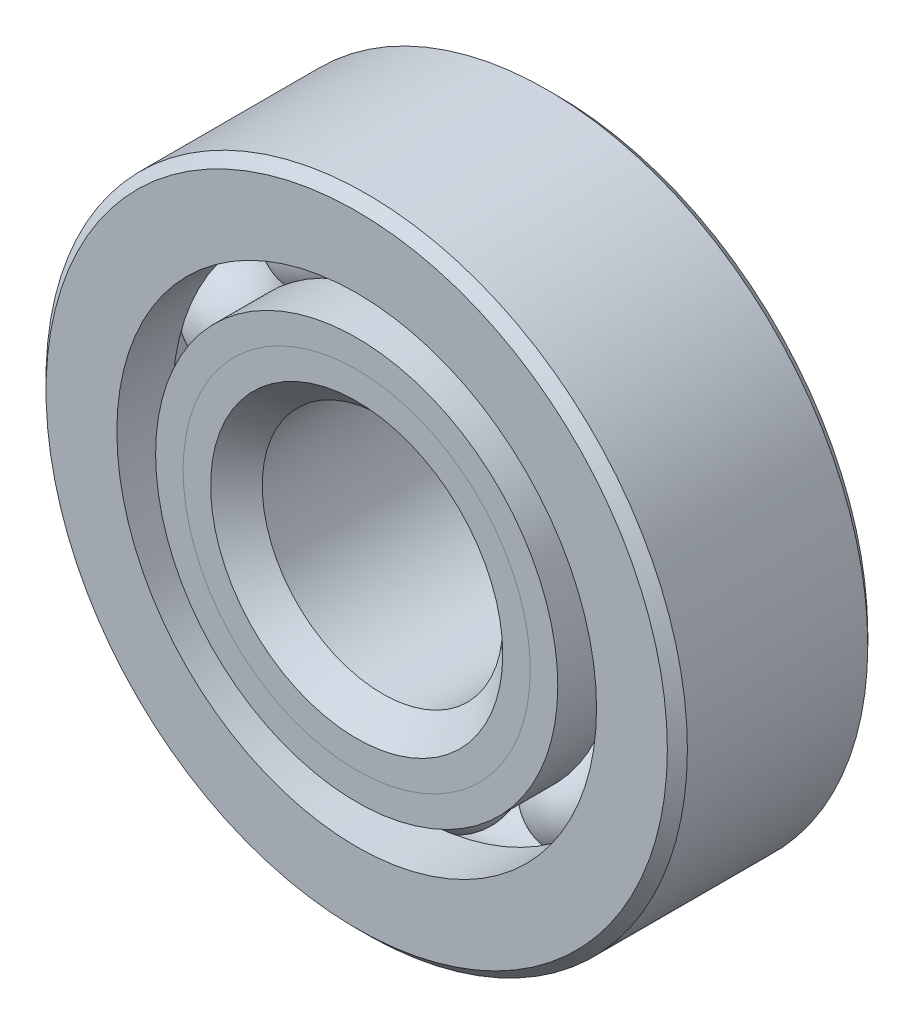
SolidWorks part; units mm, degrees
material "AISI 316 Annealed Stainless Steel Bar (SS)"
ref_plane "Front Plane" through (0, 0, 0) normal (0, 0, 1) x (1, 0, 0)
ref_plane "Top Plane" through (0, 0, 0) normal (0, 1, 0) x (1, 0, 0)
ref_plane "Right Plane" through (0, 0, 0) normal (1, 0, 0) x (0, 0, -1)
sketch "Sketch1" plane through (0, 0, 0) normal (1, 0, 0) x (0, 0, -1)
  line L0 (-1.9844, 0) -> (1.9844, 0) construction
  line L1 (0, 6.35) -> (0, -6.35) construction
  line L2 (1.7859, 6.35) -> (-1.7859, 6.35)
  line L3 (-1.7859, 6.35) -> (-1.9844, 6.1516)
  line L4 (-1.9844, 6.1516) -> (-1.9844, 4.7494)
  line L5 (-1.9844, 4.7494) -> (-0.8819, 4.7494)
  line L6 (1.9844, 4.7494) -> (0.8819, 4.7494)
  line L7 (1.9844, 6.1516) -> (1.9844, 4.7494)
  line L8 (1.7859, 6.35) -> (1.9844, 6.1516)
  line L9 (0, 6.35) -> (0, 4.3656) construction
  line L10 (0, 4.3656) -> (0, 2.3812) construction
  arc A0 (-0.8819, 4.7494) -> (0.8819, 4.7494) centre (0, 4.3656) cw
  point P14 (0, 2.3812)
  dimension "Width" = 3.9688
  dimension "OD" = 12.7
  dimension "D1" = 45
  dimension "D2" = 0.1984
  dimension "D3" = 1.7639
  dimension "D4" = 0.3838
revolve "Revolve1" add sketch "Sketch1" angle 360 about L0
sketch "Sketch2" plane through (0, 0, 0) normal (1, 0, 0) x (0, 0, -1)
  line L0 (-1.9844, 3.9818) -> (-0.8819, 3.9818)
  line L1 (-1.9844, 6.1516) -> (-1.9844, -6.1516) construction
  line L2 (-1.9844, 3.9818) -> (-1.9844, 3.4372)
  line L3 (-1.9844, 3.4372) -> (-1.4397, 2.8925)
  line L4 (-1.4397, 2.8925) -> (0, 2.8925)
  line L5 (0, 6.35) -> (0, -6.35) construction
  line L6 (0, 2.8925) -> (0, 3.4038)
  line L7 (0, 3.4038) -> (0, 2.3812) construction
  line L8 (-1.9844, 3.9818) -> (-1.9844, 2.8925) construction
  line L9 (-1.9844, 2.8925) -> (-1.4397, 2.8925) construction
  arc A0 (-0.8819, 3.9818) -> (0, 3.4038) centre (0, 4.3656) ccw
  arc A1 (0.8819, 4.7494) -> (-0.8819, 4.7494) centre (0, 4.3656) ccw construction
  circle A2 centre (0, 4.3656) radius 0.9618 construction
  dimension "D1" = 45
revolve "Revolve2" add sketch "Sketch2" angle 360 about L0
sketch "Sketch3" plane through (0, 0, 0) normal (1, 0, 0) x (0, 0, -1)
  line L0 (-1.9844, 3.4372) -> (-1.4397, 2.8925)
  line L1 (-1.4397, 2.8925) -> (0, 2.8925)
  line L2 (0, 2.8925) -> (0, 3.4038)
  line L3 (-1.9844, 3.4372) -> (-1.9844, 2.8925)
  line L4 (-1.9844, 3.9818) -> (-1.9844, 2.8925) construction
  line L5 (-1.9844, 2.8925) -> (-1.4731, 2.3812)
  line L6 (-1.4731, 2.3812) -> (1.7859, 2.3812)
  line L7 (1.7859, 6.35) -> (1.7859, -6.35) construction
  line L8 (1.7859, 2.3812) -> (1.9844, 2.5797)
  line L9 (1.9844, -6.1516) -> (1.9844, 6.1516) construction
  line L10 (1.9844, 2.5797) -> (1.9844, 3.9818)
  line L11 (1.9844, 3.9818) -> (0.8819, 3.9818)
  line L13 (1.7859, 6.35) -> (1.9844, 6.1516) construction
  circle A0 centre (0, 4.3656) radius 0.9618 construction
  arc A1 (0.8819, 3.9818) -> (0, 3.4038) centre (0, 4.3656) cw
revolve "Revolve3" add sketch "Sketch3" angle 360 about L0
sketch "Sketch4" plane through (0, 0, 0) normal (1, 0, 0) x (0, 0, -1)
  line L0 (-0.9618, 4.3656) -> (0.9618, 4.3656)
  circle A1 centre (0, 4.3656) radius 0.9618 construction
  arc A2 (-0.9618, 4.3656) -> (0.9618, 4.3656) centre (0, 4.3656) cw
  arc A3 (0.8819, 4.7494) -> (-0.8819, 4.7494) centre (0, 4.3656) ccw construction
revolve "Revolve4" add sketch "Sketch4" angle 360 about L0
ref_axis "Axis1" through (0, 0, -1.9844) along (0, 0, 1)
pattern_circular "CirPattern1" count 10 every 36 about axis through (0, 0, -1.9844) along (0, 0, 1) of bodies 104
equation "\"D2@Sketch1\" = \"Width@Sketch1\"*.05"
equation "\"D3@Sketch1\" = \"Width@Sketch1\"/2.25"
equation "\"D4@Sketch1\" = (((\"OD@Sketch1\"-\"Width@Sketch1\")/2)/3.25)/3.5"
equation "\"D2@CirPattern1\" = 360/\"Balls@CirPattern1\""
